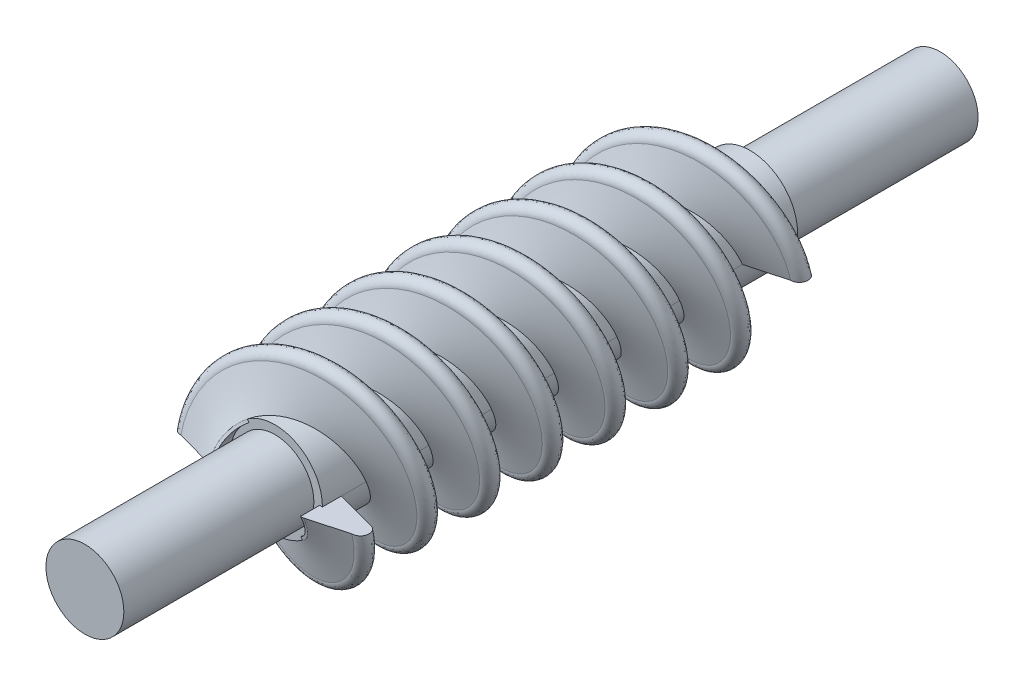
SolidWorks part; units mm, degrees
ref_plane "Plan de face" through (0, 0, 0) normal (0, 0, 1) x (1, 0, 0)
ref_plane "Plan de dessus" through (0, 0, 0) normal (0, 1, 0) x (1, 0, 0)
ref_plane "Plan de droite" through (0, 0, 0) normal (1, 0, 0) x (0, 0, -1)
sketch "Esquisse1" plane through (0, 0, 0) normal (0, 0, 1) x (1, 0, 0)
  circle A0 centre (0, 0) radius 5
  dimension "D1" = 10
extrude "Boss.-Extru.1" add sketch "Esquisse1" along normal blind 50
sketch "Esquisse3" plane through (0, 0, 50) normal (0, 0, 1) x (1, 0, 0)
  circle A0 centre (0, 0) radius 5
curve "Hélice/Spirale1" pitch 13.2 height 46.2 radius 5 centre (0, 0, 50) axis (0, 0, -1) start towards (-1, 0, 0)
sketch "Esquisse4" plane through (0, 0, 0) normal (0, 1, 0) x (1, 0, 0)
  line L0 (-5, -50) -> (-9, -50) construction
  line L1 (-5, 0) -> (-5, -50) construction
  line L2 (-9, -49.1) -> (-5, -48)
  line L3 (-9, -50.9) -> (-5, -52)
  line L5 (-5, -48) -> (-4.702, -48)
  line L6 (-4.702, -48) -> (-4.702, -52)
  line L7 (-4.702, -52) -> (-5, -52)
  arc A1 (-9, -49.1) -> (-9, -50.9) centre (-9, -50) ccw
  spline S0 degree 3 poles (-5, -50) (-5, -49.7265) (-4.7397, -49.1743) (-3.6276, -48.3502) (-1.9632, -47.525) (0, -46.7) (1.9632, -45.875) (3.6276, -45.05) (4.7397, -44.225) (5.1302, -43.4) (4.7397, -42.575) (3.6276, -41.75) (1.4084, -40.65) (-1.4084, -39.55) (-3.6276, -38.45) (-4.7397, -37.625) (-5.1302, -36.8) (-4.7397, -35.975) (-3.6276, -35.15) (-1.4084, -34.05) (1.4084, -32.95) (3.6276, -31.85) (4.7397, -31.025) (5.1302, -30.2) (4.7397, -29.375) (3.6276, -28.55) (1.4084, -27.45) (-1.4084, -26.35) (-3.6276, -25.25) (-4.7397, -24.425) (-5.1302, -23.6) (-4.7397, -22.775) (-3.6276, -21.95) (-1.4084, -20.85) (1.4084, -19.75) (3.6276, -18.65) (4.7397, -17.825) (5.1302, -17) (4.7397, -16.175) (3.6276, -15.35) (1.4084, -14.25) (-1.4084, -13.15) (-3.6276, -12.05) (-4.7397, -11.225) (-5.1302, -10.4) (-4.7397, -9.575) (-3.6276, -8.75) (-1.9632, -7.925) (0, -7.1) (1.9632, -6.275) (3.6276, -5.4498) (4.7397, -4.6257) (5, -4.0735) (5, -3.8) knots 0 0 0 0 0.017857 0.035714 0.053571 0.071429 0.089286 0.107143 0.125 0.142857 0.160714 0.178571 0.196429 0.232143 0.25 0.267857 0.285714 0.303571 0.321429 0.339286 0.375 0.392857 0.410714 0.428571 0.446429 0.464286 0.482143 0.517857 0.535714 0.553571 0.571429 0.589286 0.607143 0.625 0.660714 0.678571 0.696429 0.714286 0.732143 0.75 0.767857 0.803571 0.821429 0.839286 0.857143 0.875 0.892857 0.910714 0.928571 0.946429 0.964286 0.982143 1 1 1 1 construction
  dimension "D3" = 0.9
  dimension "D1" = 4
  dimension "D2" = 4
sweep "Balayage2" add profiles "Esquisse4" path "Hélice/Spirale1"
pattern_circular "CirPattern1" count 2 over 360 about axis through (0, 0, 50) along (0, 0, -1) of "Balayage2"
sketch "arbre" plane through (0, 0, 0) normal (0, 0, -1) x (-1, 0, 0)
  circle A0 centre (0, 0) radius 4
  dimension "D1" = 8
extrude "Boss.-Extru.3" add sketch "arbre" along normal blind 20 and the other way blind 70
sketch "Esquisse8" plane through (0, 0, 70) normal (0, 0, 1) x (1, 0, 0)
  circle A0 centre (0, 0) radius 4.1
extrude "Boss.-Extru.4" add sketch "Esquisse8" against normal blind 20
